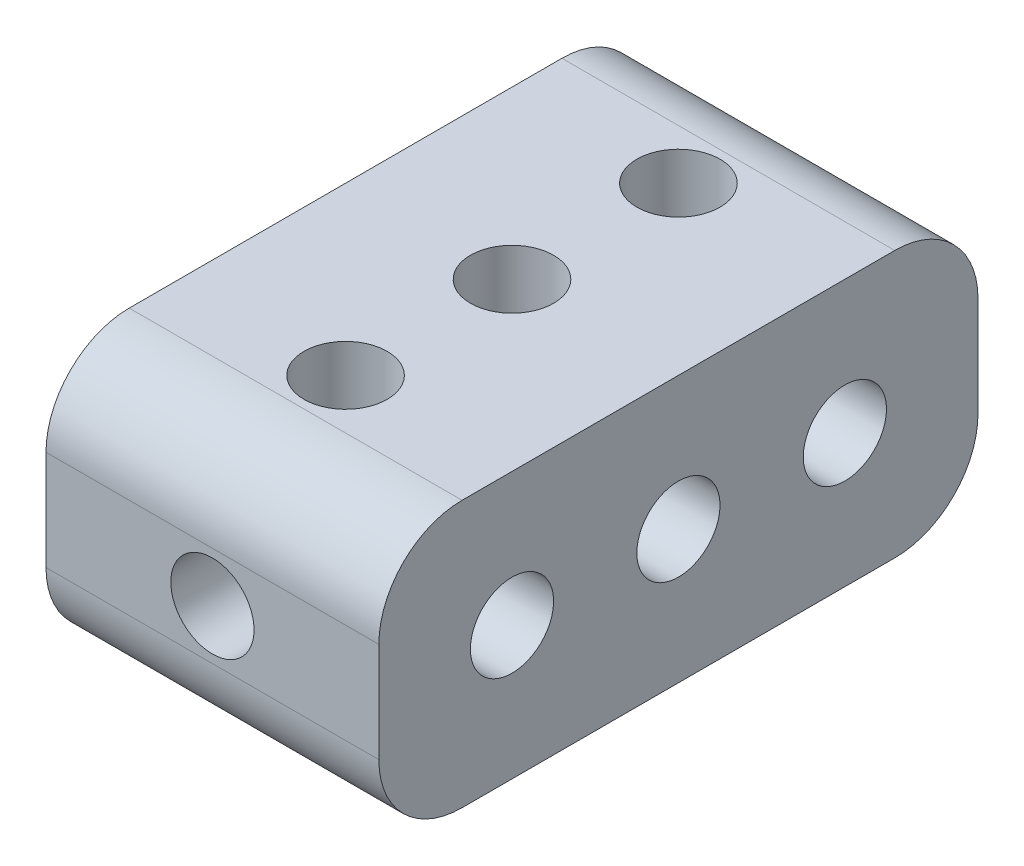
SolidWorks part; units mm, degrees
ref_plane "Front" through (0, 0, 0) normal (0, 0, 1) x (1, 0, 0)
ref_plane "Top" through (0, 0, 0) normal (0, 1, 0) x (1, 0, 0)
ref_plane "Right" through (0, 0, 0) normal (1, 0, 0) x (0, 0, -1)
sketch "Sketch1" plane through (0, 0, 0) normal (0, 1, 0) x (1, 0, 0)
  line L1 (-12.7, -22.86) -> (12.7, -22.86)
  line L2 (-12.7, -22.86) -> (-12.7, 22.86)
  line L3 (-12.7, 22.86) -> (12.7, 22.86)
  line L4 (12.7, -22.86) -> (12.7, 22.86)
  line L5 (-12.7, -22.86) -> (12.7, 22.86) construction
  line L6 (-12.7, 22.86) -> (12.7, -22.86) construction
  point P0 (0, 0)
  dimension "D1" = 25.4
  dimension "D2" = 45.72
extrude "Boss-Extrude1" add sketch "Sketch1" along normal blind 20.32
fillet "Fillet1" radius 6.35 4 edges at (0, 0, -22.86) (0, 20.32, -22.86) (0, 0, 22.86) (0, 20.32, 22.86)
sketch "Sketch2" plane through (0, 20.32, 0) normal (0, 1, 0) x (1, 0, 0)
  circle A0 centre (0, 12.7) radius 3.175
  circle A1 centre (0, 0) radius 3.175
  circle A2 centre (0, -12.7) radius 3.175
  dimension "D1" = 6.35
  dimension "D2" = 12.7
  dimension "D3" = 12.7
extrude "Cut-Extrude1" cut sketch "Sketch2" against normal through all
sketch "Sketch3" plane through (-12.7, 0, 0) normal (-1, 0, 0) x (0, 0, 1)
  line L1 (-12.7, 20.32) -> (-12.7, 10.16) construction
  line L2 (-16.51, 20.32) -> (16.51, 20.32) construction
  line L3 (-12.7, 10.16) -> (-12.7, 0) construction
  line L4 (-16.51, 0) -> (16.51, 0) construction
  circle A0 centre (-12.7, 10.16) radius 3.175
  circle A1 centre (0, 10.16) radius 3.175
  circle A2 centre (12.7, 10.16) radius 3.175
  dimension "D1" = 6.35
  dimension "D2" = 12.7
  dimension "D3" = 12.7
extrude "Cut-Extrude2" cut sketch "Sketch3" against normal through all
sketch "Sketch4" plane through (0, 0, 22.86) normal (0, 0, 1) x (1, 0, 0)
  line L1 (0, 20.32) -> (0, 10.16) construction
  line L2 (-12.7, 20.32) -> (12.7, 20.32) construction
  line L3 (0, 10.16) -> (0, 0) construction
  circle A0 centre (0, 10.16) radius 3.175
  dimension "D1" = 6.35
extrude "Cut-Extrude3" cut sketch "Sketch4" against normal through all
